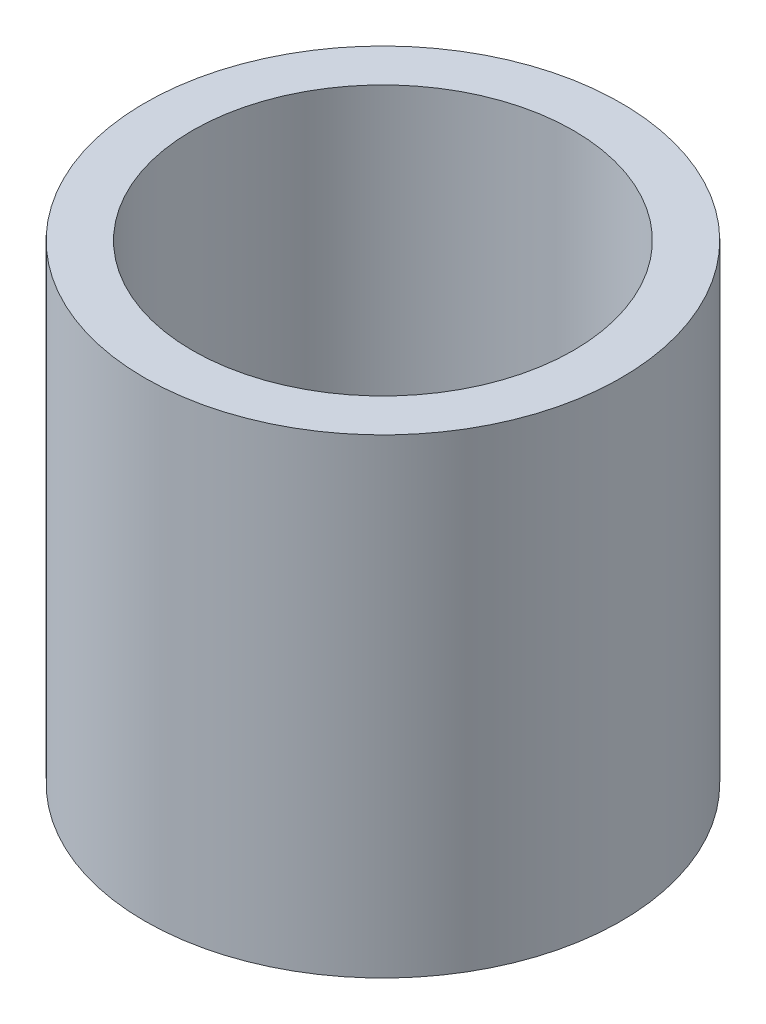
SolidWorks part; units mm, degrees
ref_plane "Front Plane" through (0, 0, 0) normal (0, 0, 1) x (1, 0, 0)
ref_plane "Top Plane" through (0, 0, 0) normal (0, 1, 0) x (1, 0, 0)
ref_plane "Right Plane" through (0, 0, 0) normal (1, 0, 0) x (0, 0, -1)
sketch "Sketch1" plane through (0, 0, 0) normal (0, 1, 0) x (1, 0, 0)
  circle A0 centre (0, 0) radius 8
  circle A1 centre (0, 0) radius 10
  dimension "D1" = 16
  dimension "D2" = 20
extrude "Boss-Extrude1" add sketch "Sketch1" along normal blind 19.75
equation "\"8mm hole\" = 8.6mm"
equation "\"22mm hole\"= 23mm"
equation "\"15mm hole\"= 16mm"
equation "\"D1@Sketch1\"= \"15mm hole\""
